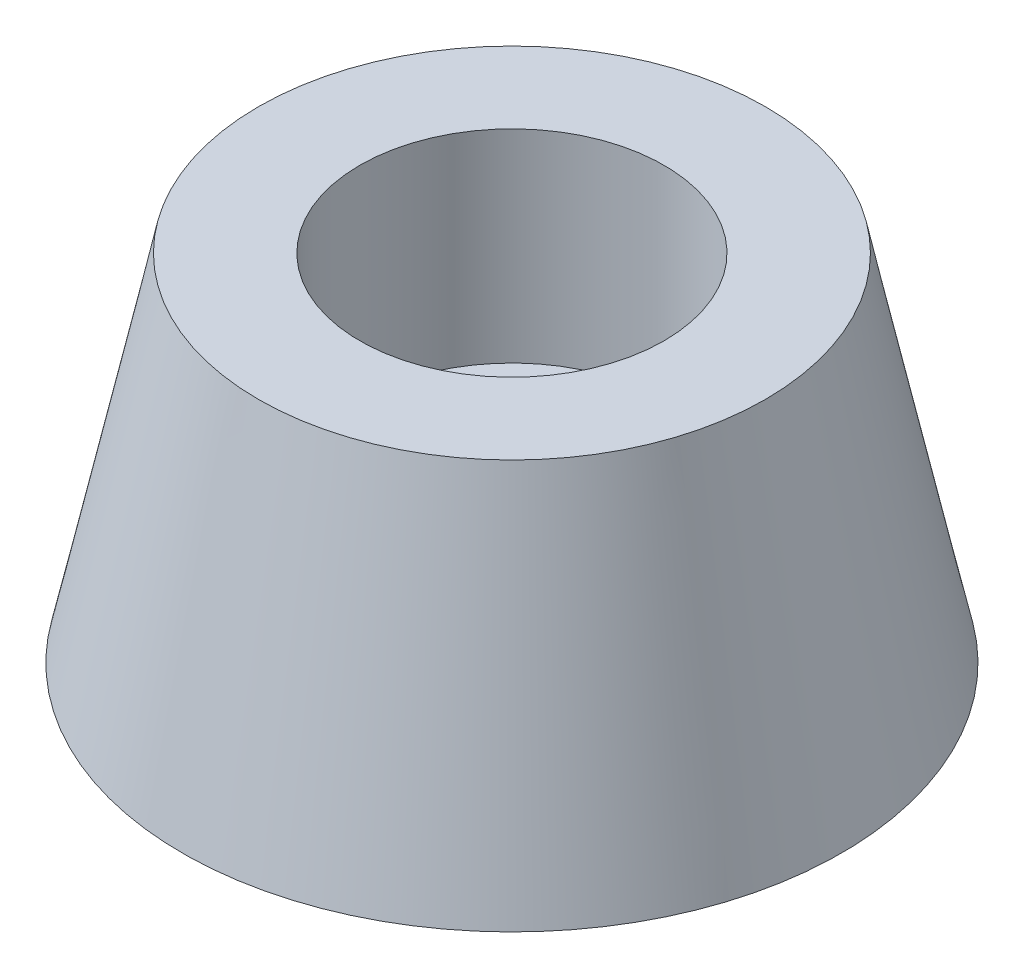
SolidWorks part; units mm, degrees
ref_plane "Front Plane" through (0, 0, 0) normal (0, 0, 1) x (1, 0, 0)
ref_plane "Top Plane" through (0, 0, 0) normal (0, 1, 0) x (1, 0, 0)
ref_plane "Right Plane" through (0, 0, 0) normal (1, 0, 0) x (0, 0, -1)
sketch "Sketch1" plane through (0, 0, 0) normal (0, 0, 1) x (1, 0, 0)
  line L0 (6.5, -7) -> (5, 0)
  line L1 (0, 0) -> (6.5, 0)
  line L2 (0, 0) -> (0, -7)
  line L3 (0, -7) -> (6.5, -7)
  line L4 (6.5, 0) -> (6.5, -7)
  dimension "D1" = 6.5
  dimension "D2" = 5
  dimension "D3" = 7
revolve "Revolve1" add sketch "Sketch1" angle 360 about L2 region at (2.8913, -3.6522, 0)
sketch "Sketch2" plane through (0, 0, 0) normal (0, 1, 0) x (1, 0, 0)
  circle A0 centre (0, 0) radius 1.65
  dimension "D1" = 3.3
extrude "Cut-Extrude1" cut sketch "Sketch2" against normal blind 10
sketch "Sketch3" plane through (0, 0, 0) normal (0, 1, 0) x (1, 0, 0)
  circle A0 centre (0, 0) radius 3
  dimension "D1" = 6
extrude "Cut-Extrude2" cut sketch "Sketch3" against normal blind 4
